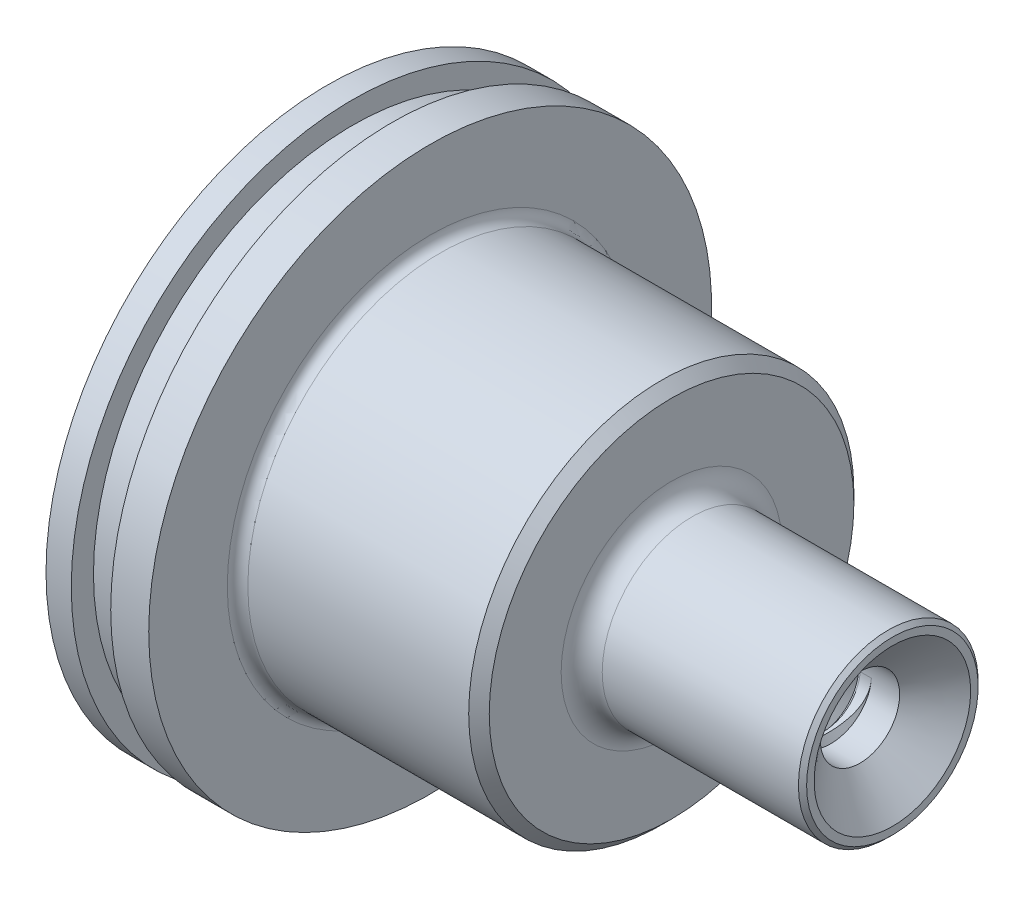
SolidWorks part; units mm, degrees
material "6061-T6 (SS)"
ref_plane "Front Plane" through (0, 0, 0) normal (0, 0, 1) x (1, 0, 0)
ref_plane "Top Plane" through (0, 0, 0) normal (0, 1, 0) x (1, 0, 0)
ref_plane "Right Plane" through (0, 0, 0) normal (1, 0, 0) x (0, 0, -1)
sketch "Sketch1" plane through (0, 0, 0) normal (0, 0, 1) x (1, 0, 0)
  line L0 (38.1, 0) -> (69.85, 0)
  line L1 (0, 19.05) -> (0, 34.798)
  line L2 (0, 34.798) -> (3.1242, 34.798)
  line L3 (3.1242, 34.798) -> (3.1242, 32.0548)
  line L4 (3.1242, 32.0548) -> (8.001, 32.0548)
  line L5 (8.001, 32.0548) -> (8.001, 34.798)
  line L6 (8.001, 34.798) -> (12.7, 34.798)
  line L7 (12.7, 34.798) -> (12.7, 23.8125)
  line L8 (12.7, 23.8125) -> (42.545, 23.8125)
  line L9 (42.545, 23.8125) -> (42.545, 11.1125)
  line L10 (42.545, 11.1125) -> (69.85, 11.1125)
  line L11 (69.85, 11.1125) -> (69.85, 0)
  line L12 (0, 19.05) -> (38.1, 19.05)
  line L13 (38.1, 19.05) -> (38.1, 0)
  line L14 (0, 0) -> (69.85, 0) construction
  dimension "D1" = 12.7
  dimension "D2" = 4.8768
  dimension "D3" = 3.1242
  dimension "D4" = 2.7432
  dimension "D5" = 34.798
  dimension "D6" = 29.845
  dimension "D7" = 27.305
  dimension "D8" = 23.8125
  dimension "D9" = 11.1125
  dimension "D10" = 19.05
  dimension "D11" = 38.1
revolve "Revolve1" add sketch "Sketch1" angle 360 about L0
fillet "Fillet1" radius 1.27 1 edges at (12.7, 0, 23.8125)
fillet "Fillet2" radius 2.54 1 edges at (42.545, 0, 11.1125)
chamfer "Chamfer1" distance 1.27 angle 45 1 edges at (42.545, 0, 23.8125)
chamfer "Chamfer2" distance 0.508 angle 45 1 edges at (69.85, 0, 11.1125)
hole_wizard "CSK for 3/8 Flat Head Machine Screw (100)1" positions "Sketch2" profile "Sketch3" countersink size "3/8" standard "ANSI Inch"
sketch "Sketch2" plane through (69.85, 0, 0) normal (1, 0, 0) x (0, 0, -1)
  point P4 (0, 0)
sketch "Sketch3" plane through (69.85, 0, 0) normal (0, 1, 0) x (0, 0, -1)
  line L0 (0, 0) -> (0, 28.3455)
  line L1 (0, 28.3455) -> (4.9022, 25.4)
  line L2 (4.9022, 25.4) -> (4.9022, 4.0069)
  line L3 (4.9022, 4.0069) -> (9.6774, 0)
  line L5 (9.6774, 0) -> (0, 0)
  line L6 (-4.9022, 4.0069) -> (-9.6774, 0) construction
  line L10 (0, 28.3455) -> (-4.9022, 25.4) construction
  line L11 (0, -6.35) -> (0, 107.95) construction
  dimension "Hole Dia." = 9.8044
  dimension "Hole Depth" = 25.4
  dimension "Near C'Sink Dia." = 19.3548
  dimension "Near C'Sink Angle" = 100
  dimension "Drill Angle" = 118
thread "Thread1" pitch 1.5875 method extrude trim with start face yes trim with end face yes profile "Thread Profile1" start angle 0, offset 2.54, length 19.05, pitch 1.5875, diameter 9.8044
ref_plane "Plane1" through (41.91, 0, -4.9022) normal (0, -1, 0) x (0, 0, -1)
sketch "Thread Profile1" plane through (41.91, 0, -4.9022) normal (0, -1, 0) x (0, 0, -1)
  line L0 (0, 0) -> (0, 1.5875) construction
  line L11 (0, 0) -> (0, 1.3891)
  line L12 (0, 1.3891) -> (-0.8593, 0.893)
  line L13 (-0.8593, 0.893) -> (-0.8593, 0.4961)
  line L15 (-0.8593, 0.4961) -> (0, 0)
  line L17 (-0.8593, 0.6945) -> (0, 0.6945) construction
  point P2 (0, 0)
  dimension "Pitch" = 1.5875
  dimension "Profile_Angle" = 60
  dimension "Profile_Land" = 0.3969
  dimension "Profile_Height" = 0.8593
sketch "Sketch4" plane through (69.85, 0, 0) normal (1, 0, 0) x (0, 0, -1)
  line L0 (4.9022, 0) -> (4.0429, 0)
  arc A0 (-0.9626, -3.9267) -> (3.9267, -0.9626) centre (0, 0) ccw construction
  arc A1 (0, -4.0429) -> (4.0429, 0) centre (0, 0) ccw
  spline S0 degree 3 poles (4.9022, 0) (4.9022, -2.8477) (2.0943, -4.0429) (0, -4.0429) knots 0 0 0 0 1 1 1 1
extrude "Cut-Extrude1" cut sketch "Sketch4" against normal blind 9.017
equation "\"D8@Sketch1\"=1.875/2"
equation "\"D9@Sketch1\"=0.875/2"
